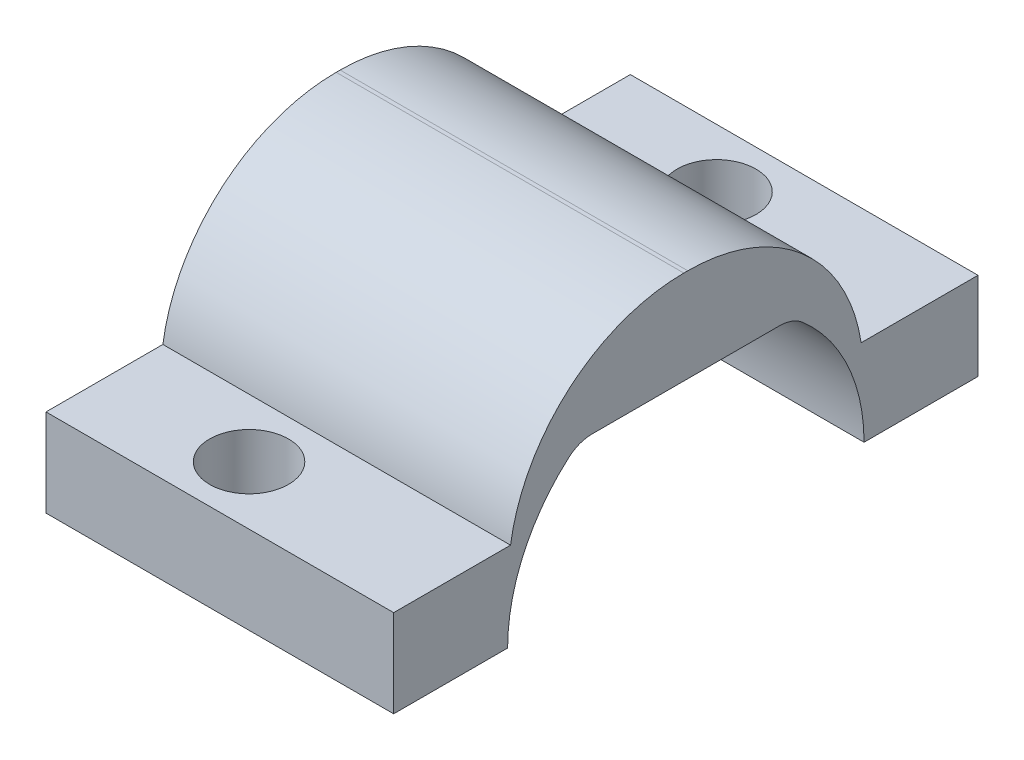
SolidWorks part; units mm, degrees
ref_plane "Plano frontal" through (0, 0, 0) normal (0, 0, 1) x (1, 0, 0)
ref_plane "Plano superior" through (0, 0, 0) normal (0, 1, 0) x (1, 0, 0)
ref_plane "Plano direito" through (0, 0, 0) normal (1, 0, 0) x (0, 0, -1)
sketch "Esboço1" plane through (0, 0, 0) normal (1, 0, 0) x (0, 0, -1)
  line L0 (0, -6.1) -> (0, -5.1)
  line L1 (0, 6.1) -> (0, 4.9)
  line L2 (-6.1, 0) -> (6.1, 0)
  line L3 (-3.6332, 4.9) -> (3.6332, 4.9)
  line L4 (-6.1, 0) -> (-10, 0)
  line L5 (6.1, 0) -> (10, 0)
  line L6 (-10, 0) -> (-10, 3)
  line L7 (10, 0) -> (10, 3)
  line L8 (-10, 3) -> (-6, 3)
  line L9 (-6, 3) -> (-6, 8.1)
  line L10 (-6, 8.1) -> (6, 8.1)
  line L11 (10, 3) -> (6, 3)
  line L12 (6, 3) -> (6, 8.1)
  circle A0 centre (0, 0) radius 6.1
  point P12 (0, 4.9)
  dimension "D1" = 12.2
  dimension "D2" = 1.2
  dimension "D3" = 1
  dimension "D4" = 3.9
  dimension "D5" = 3.9
  dimension "D6" = 3
  dimension "D7" = 3
  dimension "D8" = 2
extrude "Ressalto-extrusão1" add sketch "Esboço1" along normal blind 13.9 contours A0 L5 L7 L11 L12 L10 L9 L8 L6 L4 | L1 A0 L3 | L3 A0 L1 region at (0, 5.3843, -1.3823) region at (0, 5.9971, 1.9808) region at (0, 5.3843, 1.3823)
fillet "Filete1" radius 6 2 edges at (6.95, 8.1, 6) (6.95, 8.1, -6)
sketch "Esboço2" plane through (0, 3, 0) normal (0, 1, 0) x (1, 0, 0)
  line L0 (6.95, -6) -> (6.95, -10)
  line L1 (13.9, -6) -> (0, -6) construction
  line L2 (13.9, -10) -> (0, -10) construction
  line L3 (6.95, 6) -> (6.95, 10)
  line L4 (13.9, 6) -> (0, 6) construction
  line L5 (13.9, 10) -> (0, 10) construction
  circle A0 centre (6.95, 8) radius 1.35
  circle A1 centre (6.95, -8) radius 1.35
  dimension "D1" = 2.7
  dimension "D2" = 2.7
extrude "Corte-extrusão1" cut sketch "Esboço2" against normal blind 13.9 contours L3 A0 | L3 A0 | L0 A1 | L0 A1 region at (7.523, 3, 8) region at (6.377, 3, 8) region at (6.377, 3, -8) region at (7.523, 3, -8)
fillet "Filete2" radius 1.2 2 edges at (6.95, 4.9, -3.6332) (6.95, 4.9, 3.6332)
sketch "Esboço3" plane through (0, 3, 0) normal (0, 1, 0) x (1, 0, 0)
  line L0 (0, 10) -> (2, 10)
  line L1 (0, 10) -> (0, -10.0535)
  line L2 (2, 10) -> (2, -10.0535)
  line L3 (0, -10.0535) -> (2, -10.0535)
  line L4 (13.9, 10) -> (0, 10) construction
  dimension "D1" = 2
extrude "Corte-extrusão2" cut sketch "Esboço3" against normal through all both and the other way through all
